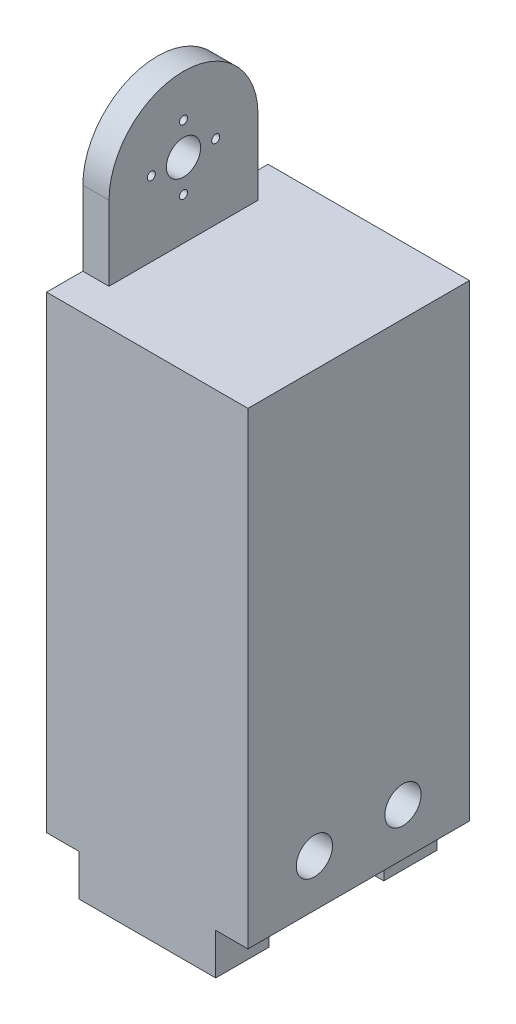
SolidWorks part; units mm, degrees
ref_plane "Front Plane" through (0, 0, 0) normal (0, 0, 1) x (1, 0, 0)
ref_plane "Top Plane" through (0, 0, 0) normal (0, 1, 0) x (1, 0, 0)
ref_plane "Right Plane" through (0, 0, 0) normal (1, 0, 0) x (0, 0, -1)
sketch "Sketch1" plane through (0, 0, 0) normal (0, 0, 1) x (1, 0, 0)
  line L1 (-25, 0) -> (25, 0)
  line L2 (-25, 0) -> (-25, -150)
  line L3 (-25, -150) -> (25, -150)
  line L4 (25, 0) -> (25, -150)
  dimension "D1" = 50
  dimension "D2" = 150
extrude "Boss-Extrude1" add sketch "Sketch1" against normal blind 55
sketch "Sketch2" plane through (25, 0, 0) normal (1, 0, 0) x (0, 0, -1)
  line L0 (55, 0) -> (0, 0) construction
  line L1 (0, -150) -> (0, 0) construction
  circle A0 centre (27.5, -25) radius 10.25
  dimension "D1" = 25
  dimension "D2" = 27.5
extrude "Cut-Extrude1" cut sketch "Sketch2" against normal blind 45 and the other way through all
sketch "Sketch7" plane through (-20, 0, 0) normal (1, 0, 0) x (0, 0, -1)
  line L0 (27.5, -17) -> (27.5, -33) construction
  circle A0 centre (27.5, -25) radius 8
  circle A1 centre (27.5, -17) radius 1
  circle A2 centre (35.5, -25) radius 1
  circle A3 centre (27.5, -33) radius 1
  circle A4 centre (19.5, -25) radius 1
  circle A5 centre (27.5, -25) radius 4.25
  point P14 (27.5, -25)
  dimension "D1" = 16
  dimension "D2" = 2
  dimension "D4" = 8.5
  dimension "D3" = 4
extrude "Cut-Extrude3" cut sketch "Sketch7" against normal blind 10 contours L0 A0 A1 | A0 A1 | A0 L0 A1 | A0 A4 | A0 A4 | L0 A3 A0 | A3 L0 A0 | A0 A3 | A0 A2 | A0 A2 | A5 L0 | L0 A5 region at (-20, -17.4355, -27.9155) region at (-20, -16.587, -27.5) region at (-20, -17.4355, -27.0845) region at (-20, -25, -29.3038) region at (-20, -25, -25.6962) region at (-20, -25, -35.913) region at (-20, -25, -35.0645) region at (-20, -25, -19.9355) region at (-20, -25, -19.087) region at (-20, -32.5645, -27.9155) region at (-20, -32.5645, -27.0845) region at (-20, -33.413, -27.5)
sketch "Sketch8" plane through (25, 0, 0) normal (1, 0, 0) x (0, 0, -1)
  line L1 (55, -150) -> (55, 0) construction
  line L3 (0, -150) -> (55, -150)
  line L4 (0, -150) -> (0, -205)
  line L5 (0, -205) -> (55, -205)
  line L6 (55, -150) -> (55, -205)
  circle A1 centre (27.5, -180) radius 10.25
  circle A3 centre (27.5, -25) radius 10.25 construction
  dimension "D1" = 27.5
  dimension "D2" = 155
  dimension "D3" = 25
extrude "Boss-Extrude2" add sketch "Sketch8" against normal blind 50
sketch "Sketch10" plane through (0, 0, 0) normal (0, 0, 1) x (1, 0, 0)
  line L0 (-25, -205) -> (25, -205) construction
  line L5 (17, -205) -> (-17, -205)
  line L6 (17, -205) -> (17, -144.75)
  line L8 (-17, -205) -> (-17, -144.75)
  line L9 (-25, 0) -> (-25, -205) construction
  line L10 (-25, -180) -> (25, -180)
  line L13 (25, -169.75) -> (-25, -169.75)
  line L14 (25, -169.75) -> (25, -190.25)
  line L15 (25, -190.25) -> (-25, -190.25)
  line L16 (-25, -169.75) -> (-25, -190.25)
  line L17 (25, -205) -> (25, 0) construction
  line L18 (0, -180) -> (17, -180)
  line L19 (0, -180) -> (0, -191.25)
  line L20 (0, -191.25) -> (17, -191.25)
  line L21 (17, -180) -> (17, -191.25)
  line L22 (17, -191.25) -> (-17, -191.25)
  line L23 (17, -191.25) -> (17, -169.75)
  line L24 (17, -169.75) -> (-17, -169.75)
  line L25 (-17, -191.25) -> (-17, -169.75)
  line L26 (17, -191.25) -> (-17, -191.25)
  line L27 (17, -191.25) -> (17, -144.75)
  line L28 (17, -144.75) -> (-17, -144.75)
  line L29 (-17, -191.25) -> (-17, -144.75)
  line L30 (-25, -169.75) -> (-17, -169.75)
  line L31 (-25, -169.75) -> (-25, -205)
  line L32 (-25, -205) -> (-17, -205)
  line L33 (-17, -169.75) -> (-17, -205)
  line L34 (25, -169.75) -> (17, -169.75)
  line L35 (25, -169.75) -> (25, -205)
  line L36 (25, -205) -> (17, -205)
  line L37 (17, -169.75) -> (17, -205)
  line L38 (-25, -169.75) -> (25, -169.75)
  line L39 (-25, -169.75) -> (-25, -164.75)
  line L40 (-25, -164.75) -> (25, -164.75)
  line L41 (25, -169.75) -> (25, -164.75)
  line M7 (-25, 0) -> (-25, -205)
  line M8 (-25, -205) -> (25, -205)
  line M9 (25, -205) -> (25, 0)
  dimension "D1" = 8
  dimension "D2" = 8
  dimension "D3" = 11.25
  dimension "D4" = 46.5
  dimension "D5" = 60.25
  dimension "D6" = 5
extrude "Cut-Extrude4" cut sketch "Sketch10" against normal through all contours L20 L22 L8 L6 M8 | L8 L15 M7 M8 | L15 L6 M9 M8 | L15 L8 L10 M7 | L8 L13 L10 M7 | L13 L6 L10 M9 | L15 L10 L6 M9 | L19 L10 L8 L15 | L10 L19 L15 L6 | L6 L13 L8 L10 | L22 L19 L15 L8 | L19 L20 L6 L15 | L29 L40 L27 L28 | L40 L8 L13 L6 region at (0, -198.125, 0) region at (21, -197.625, 0) region at (-21, -197.625, 0) region at (8.5, -190.75, 0) region at (-8.5, -190.75, 0) region at (8.5, -185.125, 0) region at (21, -185.125, 0) region at (-21, -185.125, 0) region at (-8.5, -185.125, 0) region at (0, -174.875, 0) region at (21, -174.875, 0) region at (-21, -174.875, 0) region at (0, -167.25, 0) region at (0, -154.75, 0)
sketch "Sketch11" plane through (0, -144.75, 0) normal (0, -1, 0) x (1, 0, 0)
  line L0 (17, -55) -> (17, 0) construction
  line L1 (-17, 0) -> (17, 0)
  line L2 (-17, 0) -> (-17, -13.25)
  line L3 (-17, -13.25) -> (17, -13.25)
  line L4 (17, 0) -> (17, -13.25)
  line L5 (25, -27.5) -> (-30.9131, -27.5) construction
  line L6 (25, -55) -> (25, 0) construction
  line L7 (17, -55) -> (17, -41.75)
  line L8 (-17, -41.75) -> (17, -41.75)
  line L9 (-17, -55) -> (-17, -41.75)
  line L10 (-17, -55) -> (17, -55)
  dimension "D1" = 14.25
extrude "Boss-Extrude4" add sketch "Sketch11" along normal blind 25
sketch "Sketch13" plane through (25, 0, 0) normal (1, 0, 0) x (0, 0, -1)
  line L0 (0, -169.75) -> (0, 0) construction
  line L1 (55, -169.75) -> (0, -169.75)
  line L2 (55, -169.75) -> (55, -159.75)
  line L3 (55, -159.75) -> (0, -159.75)
  line L4 (0, -169.75) -> (0, -159.75)
  dimension "D1" = 10
extrude "Cut-Extrude5" cut sketch "Sketch13" against normal blind 8
ref_plane "Plane2" through (0, 0, 0) normal (1, 0, 0) x (0, 0, -1)
mirror "Mirror2" about plane through (0, 0, 0) normal (1, 0, 0) of "Cut-Extrude5"
sketch "Sketch14" plane through (25, 0, 0) normal (1, 0, 0) x (0, 0, -1)
  line L0 (55, -159.75) -> (0, -159.75) construction
  line L1 (0, -159.75) -> (0, 0) construction
  circle A1 centre (16.5, -148) radius 5.0302
  circle A2 centre (38.5, -148) radius 5.0302
  dimension "D1" = 16.5
  dimension "D2" = 2
  dimension "D3" = 11.75
extrude "Cut-Extrude6" cut sketch "Sketch14" against normal blind 8
mirror "Mirror3" about plane through (0, 0, 0) normal (1, 0, 0) of "Cut-Extrude6"
sketch "Sketch15" plane through (0, 0, 0) normal (0, 0, 1) x (1, 0, 0)
  line L0 (-25, 0) -> (25, 0)
  line L1 (25, 0) -> (0, 0)
  line L3 (-17, -169.75) -> (17, -169.75)
  line L4 (-17, -169.75) -> (-17, -170)
  line L5 (-17, -170) -> (17, -170)
  line L6 (17, -169.75) -> (17, -170)
  line M5 (-17, -169.75) -> (17, -169.75)
  dimension "D1" = 0.25
extrude "Boss-Extrude5" add sketch "Sketch15" against normal blind 13.25 contours L6 L4 L5 M5 region at (0, -169.875, 0)
ref_plane "Plane3" through (0, 0, -27.5) normal (0, 0, 1) x (1, 0, 0)
mirror "Mirror4" about plane through (0, 0, -27.5) normal (0, 0, 1) of "Boss-Extrude5"
sketch "Sketch16" plane through (0, 0, 0) normal (0, 0, 1) x (1, 0, 0)
  line L7 (-20, -14.75) -> (-18.5, -14.75)
  line L8 (-20, -14.75) -> (-20, -35.25)
  line L9 (-20, -35.25) -> (-18.5, -35.25)
  line L10 (-18.5, -14.75) -> (-18.5, -35.25)
  line L11 (25, 0) -> (-18.5, 0)
  line L12 (25, 0) -> (25, -43.5)
  line L13 (25, -43.5) -> (-18.5, -43.5)
  line L14 (-18.5, 0) -> (-18.5, -43.5)
  line M12 (25, -159.75) -> (25, 0)
  line M13 (25, 0) -> (-25, 0)
  dimension "D1" = 1.5
  dimension "D2" = 43.5
  dimension "D3" = 43.5
extrude "Cut-Extrude7" cut sketch "Sketch16" against normal through all contours L14 L10 L13 M13 M12 region at (3.25, -21.75, 0)
sketch "Sketch19" plane through (-20, 0, 0) normal (1, 0, 0) x (0, 0, -1)
  circle A0 centre (27.5, -25) radius 4.25
  circle A1 centre (35.5, -25) radius 1
  circle A2 centre (27.5, -33) radius 1
  circle A3 centre (19.5, -25) radius 1
  circle A4 centre (27.5, -17) radius 1
  point P15 (27.5, -25)
  circle M5 centre (27.5, -25) radius 4.25
  circle M6 centre (27.5, -17) radius 1
  circle M7 centre (35.5, -25) radius 1
  circle M8 centre (27.5, -33) radius 1
  circle M9 centre (19.5, -25) radius 1
  circle M10 centre (27.5, -25) radius 10.25
  dimension "D1" = 4
extrude "Boss-Extrude6" add sketch "Sketch19" along normal blind 1.5 contours M10 M6 M8 M9 M7 M5 region at (-20, -25, -17.5399)
sketch "Sketch20" plane through (-18.5, 0, 0) normal (1, 0, 0) x (0, 0, -1)
  line L0 (0, -43.5) -> (9, -43.5)
  line L1 (9, -25) -> (9, -43.5)
  line L2 (9, -43.5) -> (0, -43.5)
  line L3 (46, -25) -> (46, -43.5)
  line L4 (46, -43.5) -> (55, -43.5)
  line L5 (46, -43.5) -> (55, -43.5)
  line L7 (9, -43.5) -> (0, -43.5)
  line L8 (9, -43.5) -> (9, -25)
  line L12 (9, -25) -> (9, -43.5)
  line L13 (9, -43.5) -> (0, -43.5)
  line L15 (0, 0) -> (55, 0)
  line L16 (0, 0) -> (0, -43.5)
  line L17 (0, -43.5) -> (55, -43.5)
  line L18 (55, 0) -> (55, -43.5)
  circle A0 centre (27.5, -25) radius 18.5
  line M6 (0, 0) -> (0, -43.5)
  line M7 (0, -43.5) -> (55, -43.5)
  line M8 (55, -43.5) -> (55, 0)
  line M9 (55, 0) -> (0, 0)
extrude "Cut-Extrude8" cut sketch "Sketch20" against normal through all contours A0 L3 L1 M7 M8 M9 M6 region at (-18.5, -21.75, -0.7012)
sketch "Sketch21" plane through (25, 0, 0) normal (1, 0, 0) x (0, 0, -1)
  circle A0 centre (16.5, -148) radius 5.0302
  circle A1 centre (16.5, -148) radius 4.5
  circle A2 centre (38.5, -148) radius 4.5
  circle A3 centre (38.5, -148) radius 5.0302
  dimension "D1" = 2
extrude "Boss-Extrude7" add sketch "Sketch21" against normal blind 8
mirror "Mirror5" about plane through (0, 0, 0) normal (1, 0, 0) of "Boss-Extrude7"
